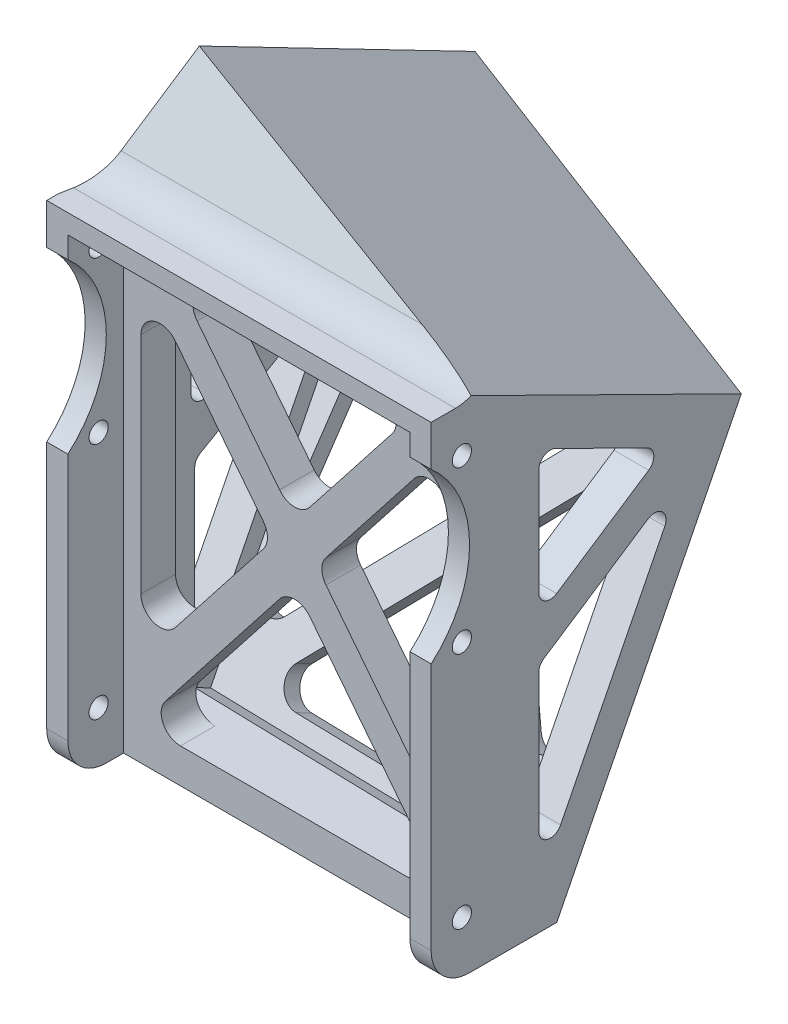
SolidWorks part; units mm, degrees
ref_plane "Front Plane" through (0, 0, 0) normal (0, 0, 1) x (1, 0, 0)
ref_plane "Top Plane" through (0, 0, 0) normal (0, 1, 0) x (1, 0, 0)
ref_plane "Right Plane" through (0, 0, 0) normal (1, 0, 0) x (0, 0, -1)
sketch "Sketch1" plane through (0, 0, 0) normal (0, 0, 1) x (1, 0, 0)
  line L1 (-25, 37.5) -> (25, 37.5)
  line L2 (-25, 37.5) -> (-25, -37.5)
  line L3 (-25, -37.5) -> (25, -37.5)
  line L4 (25, 37.5) -> (25, -37.5)
  line L5 (-25, 37.5) -> (25, -37.5) construction
  line L6 (-25, -37.5) -> (25, 37.5) construction
  point P0 (0, 0)
  dimension "D1" = 50
  dimension "D2" = 75
extrude "Boss-Extrude1" add sketch "Sketch1" along normal mid plane 50
sketch "Sketch3" plane through (0, 0, 25) normal (0, 0, 1) x (1, 0, 0)
  line L0 (-25, -37.5) -> (25, -37.5) construction
  line L1 (-22.25, 12.5) -> (22.25, 12.5)
  line L2 (-22.25, 12.5) -> (-22.25, -37.5)
  line L3 (-22.25, -37.5) -> (22.25, -37.5)
  line L4 (22.25, 12.5) -> (22.25, -37.5)
  line L5 (-22.25, 12.5) -> (22.25, -37.5) construction
  line L6 (-22.25, -37.5) -> (22.25, 12.5) construction
  point P0 (0, -12.5)
  dimension "D1" = 44.5
  dimension "D2" = 50
extrude "Cut-Extrude2" cut sketch "Sketch3" against normal blind 5.6
ref_plane "Plane1" through (18.7846, -15.6227, 40.673) normal (0.9392, -0.2961, 0.1736) x (0.023, -0.4504, -0.8925)
sketch "Sketch2" plane through (18.7846, -15.6227, 40.673) normal (0.9392, -0.2961, 0.1736) x (0.023, -0.4504, -0.8925)
  line L0 (-10.9444, 36.2708) -> (42.5099, 36.2708)
  line L3 (-10.9444, 74.2068) -> (-10.9444, 36.2708)
  line L4 (33.6826, 57.0807) -> (34.8331, 74.2068)
  line L5 (-10.9444, 36.2708) -> (33.6826, 57.0807)
  line L6 (-9.7938, 53.3969) -> (-10.9444, 36.2708)
  line L7 (34.8331, 74.2068) -> (-9.7938, 53.3969)
  line L8 (33.6826, 57.0807) -> (34.8331, 74.2068) construction
  line L9 (-10.9444, 36.2708) -> (33.6826, 57.0807) construction
  line L10 (-9.7938, 53.3969) -> (-10.9444, 36.2708) construction
  line L11 (34.8331, 74.2068) -> (-9.7938, 53.3969) construction
  line L13 (68.6118, -26.9012) -> (68.6118, 74.2068)
  line L14 (68.6118, 74.2068) -> (-10.9444, 74.2068)
  line L15 (42.5099, 36.2708) -> (42.5099, -26.9012)
  line L22 (42.5099, -26.9012) -> (68.6118, -26.9012)
  point P15 (-5.9901, 11.2025)
  dimension "D2" = 48.5
  dimension "D1" = 0
extrude "Cut-Extrude1" cut sketch "Sketch2" against normal through all both and the other way through all
sketch "Sketch5" plane through (4.3219, 10.6281, -5.2516) normal (0.3425, 0.8423, -0.4162) x (0.9395, -0.3071, 0.1517)
  line L0 (-23.2098, 14.2489) -> (-24.4872, -37.8876)
  line L1 (-31.2098, 14.4449) -> (22.0094, 13.141) construction
  line L2 (-31.2098, -39.0254) -> (22.0094, -30.0181) construction
  line L3 (-31.2098, -39.0254) -> (-31.2098, 14.4449) construction
  line L4 (-31.2098, 14.4449) -> (-23.2098, 14.2489)
  line L5 (-31.2098, 14.4449) -> (-31.2098, -39.0254)
  line L6 (-31.2098, -39.0254) -> (-24.4872, -37.8876)
  dimension "D1" = 8
extrude "Cut-Extrude4" cut sketch "Sketch5" against normal through all
sketch "Sketch6" plane through (-22.1206, 6.9746, -4.0897) normal (-0.9392, 0.2961, -0.1736) x (-0.1656, 0.0522, 0.9848)
  line L0 (29.5385, 6.6925) -> (21.4935, 23.945)
  line L1 (29.5385, 27.6964) -> (-17.7274, 5.656) construction
  line L3 (21.4935, 23.945) -> (29.5385, 27.6964)
  line L4 (29.5385, 27.6964) -> (29.5385, 6.6925)
  line L5 (-8.4538, -14.2314) -> (-17.7274, 5.656) construction
extrude "Cut-Extrude5" cut sketch "Sketch6" against normal through all
sketch "Sketch37" plane through (-25, 0, 0) normal (-1, 0, 0) x (0, 0, 1)
  line L0 (2.9555, -37.5) -> (9.0108, -49.5)
  line L1 (9.0108, -49.5) -> (25, -49.5)
  line L2 (25, -49.5) -> (25, -37.5)
  line L3 (-12.4151, -7.0396) -> (2.9555, -37.5) construction
  line L4 (25, -37.5) -> (2.9555, -37.5) construction
  line L5 (2.9555, -37.5) -> (25, -37.5)
  dimension "D1" = 12
extrude "Boss-Extrude9" add sketch "Sketch37" against normal up to surface (50 mm away) up to face at (25, -14.9462, 10.1378)
sketch "Sketch38" plane through (0, 0, 25) normal (0, 0, 1) x (1, 0, 0)
  line L0 (-22.25, -37.5) -> (-22.25, -49.5)
  line L1 (25, -49.5) -> (-25, -49.5) construction
  line L2 (-22.25, -49.5) -> (22.25, -49.5)
  line L3 (22.25, -49.5) -> (22.25, -37.5)
  line L4 (22.25, -37.5) -> (-22.25, -37.5)
  line L5 (22.25, -37.5) -> (22.25, 12.5) construction
extrude "Cut-Extrude27" cut sketch "Sketch38" against normal up to surface (5.6 mm away) up to face at (0, -12.5, 19.4)
sketch "Sketch39" plane through (0.3147, -6.1595, -12.2065) normal (0.023, -0.4504, -0.8925) x (-0.9997, -0.0104, -0.0205)
  line L1 (-31.1983, -28.5366) -> (58.2293, -28.5366)
  line L2 (-31.1983, -28.5366) -> (-31.1983, -65.0499)
  line L3 (-31.1983, -65.0499) -> (58.2293, -65.0499)
  line L4 (58.2293, -28.5366) -> (58.2293, -65.0499)
extrude "Cut-Extrude28" cut sketch "Sketch39" along normal through all
shell "Shell1" thickness 4.5
sketch "Sketch14" plane through (0, 17, 0) normal (0, 1, 0) x (1, 0, 0)
  line L4 (5.8251, -19.6931) -> (0.001, -14.9)
  line L5 (0.001, -14.9) -> (-17.6793, -14.9)
  line L6 (-17.6793, -14.9) -> (-18.4498, -19.0673)
  line L7 (-18.4498, -19.0673) -> (5.8251, -19.6931)
  line L8 (5.8251, -19.6931) -> (0.001, -14.9)
  line L9 (0.001, -14.9) -> (-17.6793, -14.9)
  line L10 (-17.6793, -14.9) -> (-18.4498, -19.0673)
  line L13 (-18.4498, -19.0673) -> (5.8251, -19.6931)
  dimension "D1" = 0
extrude "Boss-Extrude5" add sketch "Sketch14" along normal up to next
sketch "Sketch19" plane through (0, 0, 19.4) normal (0, 0, 1) x (1, 0, 0)
  line L3 (22.25, -49.5) -> (-22.25, -49.5) construction
  line L7 (-22.25, 12.5) -> (-22.25, -49.5) construction
  line L11 (22.25, -49.5) -> (22.25, 12.5) construction
  line L15 (-22.25, 12.5) -> (22.25, -44.2227) construction
  line L19 (22.25, -49.5) -> (22.25, 12.5) construction
  line L20 (22.25, 12.5) -> (-22.25, 12.5) construction
  line L24 (22.25, 12.5) -> (-22.25, -44.2227) construction
  line L25 (-22.25, 12.5) -> (-22.25, -49.5) construction
  line L28 (-15.8599, 8) -> (0, -12.2161)
  line L30 (0, -12.2161) -> (15.8599, 8)
  line L31 (15.8599, 8) -> (-15.8599, 8)
  line L33 (-20, 5.9867) -> (-2.8598, -15.8614)
  line L34 (-2.8598, -15.8614) -> (-20, -37.7095)
  line L35 (-20, -37.7095) -> (-20, 5.9867)
  line L36 (0, -19.5066) -> (-20, -45)
  line L37 (-20, -45) -> (20, -45)
  line L38 (20, -45) -> (0, -19.5066)
  line L39 (2.8598, -15.8614) -> (20, -37.7095)
  line L40 (20, -37.7095) -> (20, 5.9867)
  line L41 (20, 5.9867) -> (2.8598, -15.8614)
  dimension "D1" = 2.25
  dimension "D3" = 2.25
  dimension "D5" = 2.25
  dimension "D7" = 2.25
  dimension "D9" = 4.5
  dimension "D2" = 2.25
  dimension "D4" = 2.25
  dimension "D6" = 4.5
  dimension "D8" = 2.25
  dimension "D10" = 4.5
extrude "Cut-Extrude12" cut sketch "Sketch19" against normal blind 4.5
sketch "Sketch23" plane through (0.3147, -6.1595, -12.2065) normal (0.023, -0.4504, -0.8925) x (-0.9997, -0.0104, -0.0205)
  line L5 (-20.2942, -46.0111) -> (20.7166, -45.5349)
  line L7 (-20.2942, -46.0111) -> (20.7166, -45.5349)
  line L13 (20.7166, -45.5349) -> (20.7166, -1.1994)
  line L19 (-20.2942, 1.24) -> (-20.2942, -46.0111)
  line L22 (15.1175, 14.1541) -> (-20.2942, 1.24)
  line L23 (20.7166, -1.1994) -> (15.1175, 14.1541)
  line L26 (20.7166, -45.5349) -> (20.7166, -1.1994)
  line L32 (-20.2942, 1.24) -> (-20.2942, -46.0111)
  line L35 (15.1175, 14.1541) -> (-20.2942, 1.24)
  line L36 (20.7166, -1.1994) -> (15.1175, 14.1541)
  dimension "D1" = 0
extrude "Cut-Extrude14" cut sketch "Sketch23" against normal up to next from offset 2.25 offset against normal yes
sketch "Sketch25" plane through (0.3147, -6.1595, -12.2065) normal (0.023, -0.4504, -0.8925) x (-0.9997, -0.0104, -0.0205)
  line L0 (-20.2942, 1.24) -> (20.7166, -45.5349) construction
  line L1 (-20.2942, -46.0111) -> (15.1175, 14.1541) construction
  line L2 (15.1175, 14.1541) -> (20.7166, -45.5349) construction
  line L3 (-20.2942, -2.1729) -> (-6.418, -17.9994)
  line L4 (-6.418, -17.9994) -> (-20.2942, -41.5753)
  line L5 (20.7166, -1.1994) -> (15.1175, 14.1541)
  line L6 (20.7166, -45.5349) -> (20.7166, -1.1994)
  line L7 (-20.2942, -46.0111) -> (20.7166, -45.5349)
  line L8 (-20.2942, 1.24) -> (-20.2942, -46.0111)
  line L9 (15.1175, 14.1541) -> (-20.2942, 1.24)
  line L10 (20.7166, -1.1994) -> (15.1175, 14.1541) construction
  line L11 (20.7166, -45.5349) -> (20.7166, -1.1994) construction
  line L13 (-20.2942, 1.24) -> (-20.2942, -46.0111) construction
  line L14 (15.1175, 14.1541) -> (-20.2942, 1.24) construction
  line L15 (-20.2942, -41.5753) -> (-20.2942, -2.1729)
  line L16 (-18.0268, 2.0669) -> (-4.0142, -13.9152)
  line L17 (-4.0142, -13.9152) -> (11.7931, 12.9417)
  line L18 (11.7931, 12.9417) -> (-18.0268, 2.0669)
  line L19 (15.4764, 10.3281) -> (-0.8899, -17.4786)
  line L20 (-0.8899, -17.4786) -> (20.3581, -41.7131)
  line L21 (20.3581, -41.7131) -> (15.4764, 10.3281)
  line L22 (-16.332, -43.715) -> (-3.2938, -21.5628)
  line L23 (-3.2938, -21.5628) -> (15.8015, -43.3418)
  line L24 (15.8015, -43.3418) -> (-16.332, -43.715)
  line L30 (-20.2942, -46.0111) -> (20.7166, -45.5349)
  dimension "D3" = 2.25
  dimension "D5" = 2.25
  dimension "D2" = 4.5
  dimension "D4" = 4.5
  dimension "D6" = 2.25
extrude "Cut-Extrude18" cut sketch "Sketch25" against normal up to next contours L24 L23 L22 | L20 L21 L19 | L17 L18 L16 | L15 L4 L3 region at (15.9794, -24.3727, -2.6121) region at (3.7298, -5.7987, -12.3005) region at (-11.3304, -20.8217, -5.1081) region at (1.5891, -38.4706, 4.1308)
sketch "Sketch26" plane through (25, 0, 0) normal (1, 0, 0) x (0, 0, -1)
  line L0 (-14.9, -45) -> (-12.9549, -45) construction
  line L7 (-25, -49.5) -> (-10.2999, -49.5) construction
  line L8 (8.3318, -2.8154) -> (-14.9, -18.168) construction
  line L9 (3.8238, -3.0976) -> (-12.65, -13.9842)
  line L10 (-14.9, -45) -> (-12.9549, -45)
  line L11 (-14.9, 8.664) -> (-14.9, -45)
  line L12 (8.3318, -2.8154) -> (-14.9, 8.664)
  line L13 (-12.9549, -45) -> (8.3318, -2.8154)
  line L14 (3.8238, -3.0976) -> (-12.65, 5.0425)
  line L19 (-14.9, 8.664) -> (-14.9, -45) construction
  line L20 (8.3318, -2.8154) -> (-14.9, 8.664) construction
  line L21 (-12.9549, -45) -> (8.3318, -2.8154) construction
  line L22 (3.8238, -3.0976) -> (-15.8967, 6.6468) construction
  line L23 (3.8238, -3.0976) -> (-16.1405, -16.2909) construction
  line L24 (-12.65, 5.0425) -> (-12.65, -13.9842)
  line L25 (-12.65, -19.378) -> (6.29, -6.8616)
  line L26 (6.29, -6.8616) -> (-12.65, -44.3957)
  line L27 (-12.65, -44.3957) -> (-12.65, -19.378)
  dimension "D3" = 2.25
  dimension "D2" = 2.25
  dimension "D4" = 2.25
extrude "Cut-Extrude19" cut sketch "Sketch26" against normal up to next contours L14 L24 L9 | L27 L26 L25 | L24 L9 L14 | L27 L25 L26 region at (25, -4.0131, 7.1587) region at (25, -23.5451, 6.3367)
sketch "Sketch27" plane through (-25, 0, 0) normal (-1, 0, 0) x (0, 0, 1)
  line L0 (-8.0754, -5.4183) -> (14.9, -18.4731) construction
  line L8 (14.9, -18.4731) -> (14.9, -45) construction
  line L9 (14.9, -18.4731) -> (14.9, 8.0539) construction
  line L10 (-6.2446, -9.0464) -> (11.8979, -45)
  line L11 (14.9, -45) -> (14.9, 8.0539)
  line L12 (11.8979, -45) -> (14.9, -45)
  line L13 (-8.0754, -5.4183) -> (11.8979, -45)
  line L14 (14.9, 8.0539) -> (-8.0754, -5.4183)
  line L24 (11.8979, -45) -> (14.9, -45) construction
  line L27 (-8.0754, -5.4183) -> (11.8979, -45) construction
  line L28 (14.9, 8.0539) -> (-8.0754, -5.4183) construction
  line L29 (11.8979, -45) -> (11.8979, -19.3551)
  line L30 (11.8979, -19.3551) -> (-6.2446, -9.0464)
  line L31 (-3.0749, -5.3843) -> (12.4, -14.1772)
  line L32 (12.4, -14.1772) -> (12.4, 3.6898)
  line L33 (12.4, 3.6898) -> (-3.0749, -5.3843)
  dimension "D2" = 2.25
  dimension "D3" = 2.5
extrude "Cut-Extrude20" cut sketch "Sketch27" against normal up to next contours L29 L30 L10 | L32 L33 L31 region at (-25, -24.4672, 5.8504) region at (-25, -5.2905, 7.2417)
sketch "Sketch28" plane through (-22.1206, 6.9746, -4.0897) normal (-0.9392, 0.2961, -0.1736) x (-0.1656, 0.0522, 0.9848)
  line L0 (-6.8798, -12.2829) -> (18.4892, 17.5789) construction
  line L1 (2.4946, -4.7236) -> (18.4892, 4.0853)
  line L2 (18.4892, 4.0853) -> (18.4892, 14.1037)
  line L3 (18.4892, 14.1037) -> (2.4946, -4.7236)
  line L4 (-8.3663, -3.7711) -> (-11.7472, 3.4794)
  line L5 (-11.7472, 3.4794) -> (13.6, 15.299)
  line L6 (-8.3663, -3.7711) -> (1.1815, 0.6811)
  line L7 (18.4892, 1.5166) -> (18.4892, 17.5789)
  line L8 (-4.8406, -11.332) -> (18.4892, 1.5166)
  line L9 (-4.8406, -11.332) -> (18.4892, 1.5166)
  line L10 (-13.7864, 2.5285) -> (-6.8798, -12.2829)
  line L11 (18.4892, 17.5789) -> (-13.7864, 2.5285)
  line L13 (18.4892, 1.5166) -> (18.4892, 17.5789) construction
  line L16 (-13.7864, 2.5285) -> (-6.8798, -12.2829) construction
  line L17 (18.4892, 17.5789) -> (-13.7864, 2.5285) construction
  line L18 (13.6, 15.299) -> (1.1815, 0.6811)
  line L24 (-6.8798, -12.2829) -> (-4.8406, -11.332)
  line L25 (-6.8798, -12.2829) -> (-4.8406, -11.332)
  dimension "D3" = 2.25
  dimension "D5" = 2.25
  dimension "D2" = 2.25
  dimension "D4" = 4.5
  dimension "D6" = 8
extrude "Cut-Extrude21" cut sketch "Sketch28" against normal up to surface (4.5 mm away) contours L18 L5 L4 | L2 L3 L1 region at (-22.9499, 11.9424, 8.868) region at (-20.5288, 11.4503, -5.0667)
sketch "Sketch29" plane through (4.3219, 10.6281, -5.2516) normal (0.3425, 0.8423, -0.4162) x (0.9395, -0.3071, 0.1517)
  line L5 (-24.1693, -24.9136) -> (-24.3342, -31.6429)
  line L6 (-24.2698, -29.0136) -> (-23.2098, 14.2489) construction
  line L7 (-24.1693, -24.9136) -> (25.1433, -24.9136)
  line L9 (25.1433, -24.9136) -> (24.9488, -32.8504)
  line L10 (-24.3342, -31.6429) -> (24.9488, -32.8504)
  line L11 (21.3419, -30.1311) -> (-24.2698, -29.0136) construction
  dimension "D1" = 4.1
extrude "Cut-Extrude22" cut sketch "Sketch29" against normal offset from surface (16.724 mm away) 2.5 up to face at (0, 12.5, 22.2)
sketch "Sketch31" plane through (0, 0, 25) normal (0, 0, 1) x (1, 0, 0)
  line L3 (25, -49.5) -> (25, 15)
  line L4 (25, -49.5) -> (25, 15)
  line L5 (25, 15) -> (-23.038, 15)
  line L6 (25, 15) -> (-25, 15)
  line L16 (-25, 14.8998) -> (-25, -49.5)
  line L29 (-23.038, 15) -> (-25, 14.8998)
  line L30 (-25, 15) -> (-25, -49.5)
  line L32 (-22.25, -49.5) -> (-22.25, 12.5)
  line L33 (-22.25, -49.5) -> (-22.25, 12.5)
  line L34 (-22.25, 12.5) -> (22.25, 12.5)
  line L35 (-22.25, 12.5) -> (22.25, 12.5)
  line L36 (22.25, 12.5) -> (22.25, -49.5)
  line L37 (22.25, 12.5) -> (22.25, -49.5)
  line L38 (-25, -49.5) -> (-22.25, -49.5)
  line L39 (-25, -49.5) -> (-22.25, -49.5)
  line L40 (22.25, -49.5) -> (25, -49.5)
  line L41 (22.25, -49.5) -> (25, -49.5)
  dimension "D1" = 0
extrude "Boss-Extrude6" add sketch "Sketch31" along normal blind 1.65 and the other way blind 0.1
sketch "Sketch30" plane through (-25, 0, 0) normal (-1, 0, 0) x (0, 0, 1)
  line L0 (36.15, -1.25) -> (26.65, -1.25) construction
  line L2 (24.9, 15) -> (20.3773, 15) construction
  line L3 (26.65, 9.7045) -> (26.65, -12.2045)
  line L4 (26.65, 15) -> (26.65, -49.5) construction
  circle A0 centre (36.15, -1.25) radius 13 construction
  arc A1 (26.65, 9.7045) -> (26.65, -12.2045) centre (36.15, -1.25) ccw
  dimension "D1" = 16.25
  dimension "D3" = 26
  dimension "D4" = 1.5
  dimension "D2" = 9.5
extrude "Cut-Extrude23" cut sketch "Sketch30" against normal through all
sketch "Sketch32" plane through (-22.1206, 6.9746, -4.0897) normal (-0.9392, 0.2961, -0.1736) x (-0.1656, 0.0522, 0.9848)
  line L1 (28.0651, 7.7221) -> (32.0751, 7.7221)
  line L2 (28.0651, 7.7221) -> (28.0651, 5.2637)
  line L3 (28.0651, 5.2637) -> (32.0751, 5.2637)
  line L4 (32.0751, 7.7221) -> (32.0751, 5.2637)
extrude "Cut-Extrude24" cut sketch "Sketch32" along normal through all
sketch "Sketch34" plane through (-25, 0, 0) normal (-1, 0, 0) x (0, 0, 1)
  line L0 (22.65, 9.25) -> (22.65, -11.75) construction
  line L2 (26.65, 15) -> (26.65, 9.7045) construction
  line L3 (22.65, 9.25) -> (26.65, 9.25) construction
  line L4 (25.171, 15) -> (20.3773, 15) construction
  line L5 (22.65, -11.75) -> (22.65, -42.75) construction
  circle A0 centre (22.65, 9.25) radius 1.25
  circle A1 centre (22.65, -11.75) radius 1.25
  circle A2 centre (22.65, -42.75) radius 1.25
  dimension "D1" = 2.5
  dimension "D2" = 4
  dimension "D3" = 5.75
  dimension "D4" = 21
  dimension "D5" = 52
extrude "Cut-Extrude25" cut sketch "Sketch34" against normal through all
fillet "Fillet2" radius 2.5 12 edges at (20, 5.9867, 17.15) (0, -19.5066, 17.15) (0, -12.2161, 17.15) (-2.8598, -15.8614, 17.15) (-20, 5.9867, 17.15) (-20, -37.7095, 17.15) (20, -37.7095, 17.15) (20, -45, 17.15) (-20, -45, 17.15) (2.8598, -15.8614, 17.15) (-15.8599, 8, 17.15) (15.8599, 8, 17.15)
fillet "Fillet3" radius 2.5 7 edges at (-18.8283, 20.7247, 14.5093) (-21.8409, 1.9335, -1.2424) (-17.0156, 9.0132, -15.2678) (-17.6591, 21.6094, 9.6944) (-21.8409, 11.17, 14.5093) (-19.9982, 7.0196, -2.5355) (-19.7557, 2.2749, -11.9382)
fillet "Fillet5" radius 2.5 12 edges at (20.5777, -42.5599, 7.9443) (4.302, -18.0344, -4.8511) (6.7052, -21.6557, -2.9618) (1.1785, -21.2481, -3.31) (-15.5085, -44.5112, 7.9986) (16.6165, -44.5112, 8.8268) (3.5817, -24.8694, -1.4207) (-11.5012, 5.779, -17.275) (-15.1834, 3.4074, -16.1732) (-20.0639, -43.1043, 7.1712) (20.5777, -7.3824, -9.8066) (18.3109, -3.6207, -11.7632)
fillet "Fillet6" radius 5 1 edges at (0.2994, 15, 20.3773)
fillet "Fillet7" radius 1.5 6 edges at (22.75, -44.3957, 12.65) (22.75, -6.8616, -6.29) (22.75, -19.378, 12.65) (22.75, -13.9842, 12.65) (22.75, 5.0425, 12.65) (22.75, -3.0976, -3.8238)
fillet "Fillet8" radius 1.5 6 edges at (-22.75, -14.1772, 12.4) (-22.75, -5.3843, -3.0749) (-22.75, 3.6898, 12.4) (-22.75, -45, 11.8979) (-22.75, -19.3551, 11.8979) (-22.75, -9.0464, -6.2446)
fillet "Fillet9" radius 5 2 edges at (23.625, -49.5, 26.65) (-23.625, -49.5, 26.65)
equation "\"t\"= 4.5mm"
equation "\"D1@Shell1\"=\"t\""
equation "\"D1@Sketch19\"=\"t\"/2"
equation "\"D7@Sketch19\"=\"t\"/2"
equation "\"D3@Sketch19\"=\"t\"/2"
equation "\"D5@Sketch19\"=\"t\"/2"
equation "\"D1@Cut-Extrude12\"=\"t\""
equation "\"D19@Cut-Extrude14\"=\"t\"/2"
equation "\"D2@Sketch25\"=\"t\""
equation "\"D3@Sketch25\"=\"t\"/2"
equation "\"D4@Sketch25\"=\"t\""
equation "\"D5@Sketch25\"=\"t\"/2"
equation "\"D3@Sketch28\"=\"t\"/2"
equation "\"D4@Sketch28\"=\"t\""
equation "\"D5@Sketch28\"=\"t\"/2"
equation "\"D9@Sketch19\"=\"t\""
equation "\"D2@Sketch19\"=\"t\"/2"
equation "\"D4@Sketch19\"=\"t\"/2"
equation "\"D6@Sketch19\"=\"t\""
equation "\"D8@Sketch19\"=\"t\"/2"
equation "\"D10@Sketch19\"=\"t\""
equation "\"D6@Sketch25\"=\"t\"/2"
equation "\"D2@Sketch26\"=\"t\"/2"
equation "\"D3@Sketch26\"=\"t\"/2"
equation "\"D4@Sketch26\"=\"t\"/2"
equation "\"D2@Sketch27\"=\"t\"/2"
equation "\"D2@Sketch28\"=\"t\"/2"
